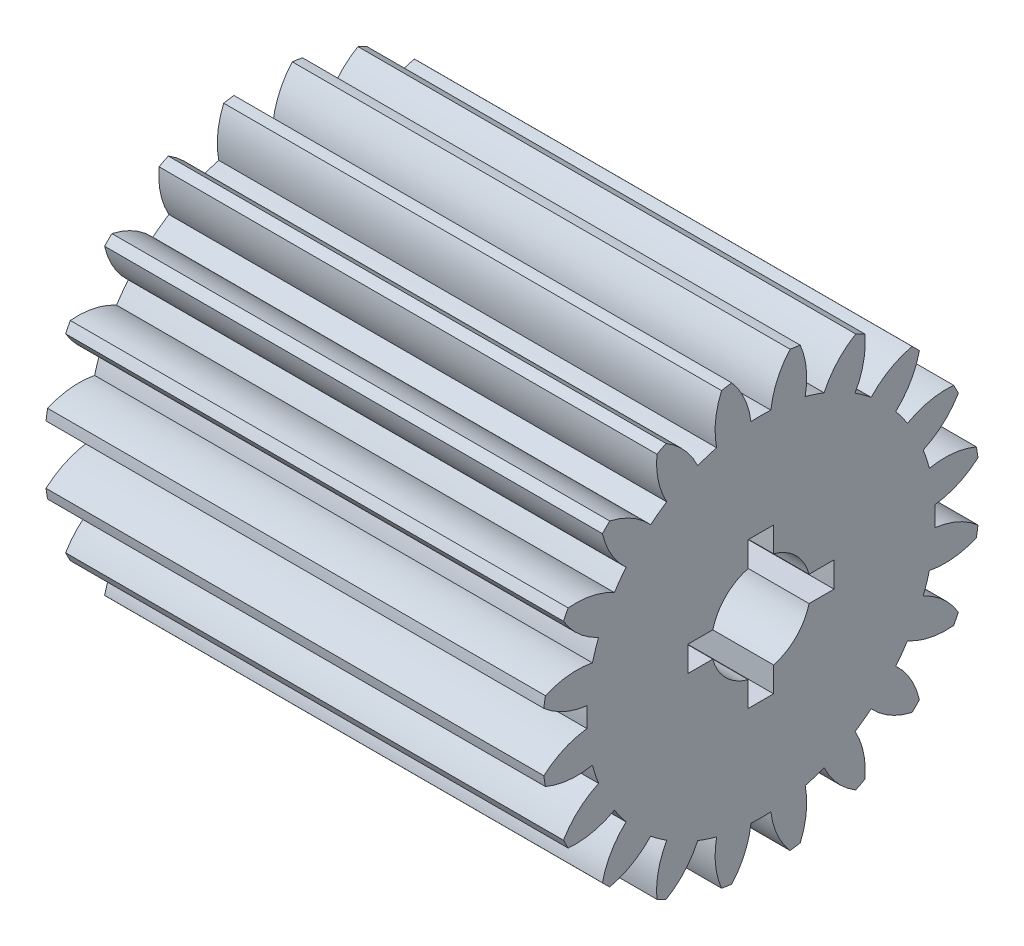
SolidWorks part; units mm, degrees
material "AISI 1020"
ref_plane "Plane1" through (0, 0, 0) normal (0, 0, 1) x (1, 0, 0)
ref_plane "Plane2" through (0, 0, 0) normal (0, 1, 0) x (1, 0, 0)
ref_plane "Plane3" through (0, 0, 0) normal (1, 0, 0) x (0, 0, -1)
other "Configuration Table"
sketch "HoldingSke" plane through (0, 0, 0) normal (0, 1, 0) x (1, 0, 0)
  line L0 (0, 0) -> (2.3492, -0.8551)
  line L1 (-15, 0) -> (100, 0) construction
  line L2 (0, 0) -> (-2.1039, 2.3779)
  line L3 (0, 0) -> (-11.863, 4.5341)
  line L4 (0, 0) -> (8.1152, 2.9537)
  line L5 (0, 0) -> (-46.8476, -17.4728)
  line L6 (0, 0) -> (-8.2896, -5.593)
  line L7 (-2.1039, 2.3779) -> (8.6586, 51.2059)
  line L8 (-76.2, 54.61) -> (-75.9, 54.61)
  line L9 (-71.009, 38.7566) -> (-53.1078, 45.2721)
  line L10 (-76.2, 71.12) -> (104.1128, 71.12)
  line L11 (0, 0) -> (-10, 0)
  line L12 (-76.2, 101.6) -> (-76.185, 101.6)
  line L13 (24.9733, 27.94) -> (52.9518, 28.4284)
  line L14 (24.9733, 27.94) -> (24.9743, 27.94)
  line L15 (24.9733, 27.94) -> (100.4006, 29.5858)
  line L16 (-63.627, -0.4) -> (-12.827, -0.4)
  circle A0 centre (0, 0) radius 1
  circle A1 centre (0, 0) radius 3.499
  circle A2 centre (0, 0) radius 37.5
  circle A3 centre (0, 0) radius 1
  dimension "Num_teeth" = 20
  dimension "Pitch_radius" = 180.3128
  dimension "Width" = 10
  dimension "Thickness" = 10
sketch "BasProSke" plane through (0, 0, 0) normal (0, 1, 0) x (1, 0, 0)
  line L0 (-10, 0) -> (60, 0) construction
  line L1 (0, 0) -> (0, 4.4)
  line L2 (0, 0) -> (10, 0)
  line L3 (10, 0) -> (10, 4.4)
  line L4 (10, 4.4) -> (0, 4.4)
  dimension "Thickness" = 10
  dimension "Diameter" = 8.8
revolve "Base-Revolve" add sketch "BasProSke" angle 360 about L0
sketch "TooCutSke" plane through (0, 0, 0) normal (1, 0, 0) x (0, 0, -1)
  line L1 (0, 0) -> (0, 107) construction
  line L2 (0, 0) -> (-0.3401, 3.9855) construction
  line L3 (0, 0) -> (-1.2482, 7.8811) construction
  line L4 (-0.3401, 3.9855) -> (-0.6241, 3.9405) construction
  arc A0 (0.1996, 3.4933) -> (-0.1996, 3.4933) centre (0, 0) ccw
  arc A1 (0.606, 4.3837) -> (-0.606, 4.3837) centre (0, 0) ccw
  circle A2 centre (0, 0) radius 4 construction
  circle A3 centre (0, 0) radius 3.7588 construction
  arc A4 (-0.1996, 3.4933) -> (-0.606, 4.3837) centre (-1.7886, 3.306) ccw
  arc A5 (0.606, 4.3837) -> (0.1996, 3.4933) centre (1.7886, 3.306) ccw
extrude "ToothCut" cut sketch "TooCutSke" along normal through all
fillet "Breaks" [suppressed] radius 0.008 tangent propagation no
fillet "RootFillets" [suppressed] radius 0.101
pattern_circular "TeethCuts" count 20 every 18 about axis through (-10, 0, 0) along (1, 0, 0) of "ToothCut", "RootFillets", "Breaks"
sketch "HubNeaOneSke" plane through (0, 0, 0) normal (-1, 0, 0) x (0, 0, 1)
  circle A0 centre (0, 0) radius 3.499
  dimension "Diameter" = 6.998
extrude "HubNearOne" [suppressed] add sketch "HubNeaOneSke" along normal blind 40.0001
sketch "HubNeaBotSke" plane through (0, 0, 0) normal (-1, 0, 0) x (0, 0, 1)
  circle A0 centre (0, 0) radius 3.499
  dimension "Diameter" = 6.998
extrude "HubNearBoth" [suppressed] add sketch "HubNeaBotSke" along normal blind 20
ref_plane "FarPln" through (10, 0, 0) normal (1, 0, 0) x (0, 0, -1)
sketch "HubFarSke" plane through (10, 0, 0) normal (1, 0, 0) x (0, 0, -1)
  circle A0 centre (0, 0) radius 3.499
  dimension "Diameter" = 6.998
extrude "HubFar" [suppressed] add sketch "HubFarSke" along normal blind 20
sketch "BorSke" plane through (0, 0, 0) normal (1, 0, 0) x (0, 0, -1)
  circle A0 centre (0, 0) radius 1
  dimension "Diameter" = 2
extrude "Bore" cut sketch "BorSke" along normal mid plane 100.0001
sketch "KeySke" plane through (0, 0, 0) normal (1, 0, 0) x (0, 0, -1)
  line L0 (-0.4, 0) -> (-0.4, 1.3)
  line L1 (-0.4, 1.3) -> (0.4, 1.3)
  line L2 (0.4, 1.3) -> (0.4, 0)
  line L3 (0, 0) -> (0, 34) construction
  line L4 (-0.4, 0) -> (0.4, 0)
  dimension "Width" = 0.8
extrude "Keyway" [suppressed] cut sketch "KeySke" along normal mid plane 100.0001
pattern_circular "Keyway2" [suppressed] count 2 every 90 about axis through (-10, 0, 0) along (1, 0, 0) reverse direction yes
sketch "Sketch1" plane through (10, 0, 0) normal (1, 0, 0) x (0, 0, -1)
  line L0 (-0.255, 0.9587) -> (0.255, 0.9587)
  line L1 (-0.255, 0.9587) -> (-0.255, 1.4687)
  line L2 (0.255, 0.9587) -> (0.255, 1.4687)
  line L3 (-0.255, 1.4687) -> (0.255, 1.4687)
  line L4 (0.9587, 0.255) -> (0.9587, -0.255)
  line L5 (0.9587, 0.255) -> (1.4687, 0.255)
  line L6 (0.9587, -0.255) -> (1.4687, -0.255)
  line L7 (1.4687, 0.255) -> (1.4687, -0.255)
  line L8 (0.255, -0.9587) -> (-0.255, -0.9587)
  line L9 (0.255, -0.9587) -> (0.255, -1.4687)
  line L10 (-0.255, -0.9587) -> (-0.255, -1.4687)
  line L11 (0.255, -1.4687) -> (-0.255, -1.4687)
  line L12 (-0.9587, -0.255) -> (-0.9587, 0.255)
  line L13 (-0.9587, -0.255) -> (-1.4687, -0.255)
  line L14 (-0.9587, 0.255) -> (-1.4687, 0.255)
  line L15 (-1.4687, -0.255) -> (-1.4687, 0.255)
  circle A0 centre (0, 0) radius 0.992
  dimension "D2" = 1.984
  dimension "D1" = 0.51
  dimension "D3" = 0.51
  dimension "D4" = 0.51
  dimension "D5" = 0.51
  dimension "D6" = 0.51
  dimension "D7" = 0.51
  dimension "D8" = 0.51
  dimension "D9" = 0.51
extrude "Cut-Extrude1" cut sketch "Sketch1" against normal blind 100 contours L3 L2 L0 L1 | L5 L7 L6 L4 | L9 L11 L10 L8 | L13 L15 L14 L12
equation "' \"Module@HoldingSke\" = 6.35"
equation "' \"Num_teeth@HoldingSke\" = 12"
equation "' \"Ap@HoldingSke\" =  20"
equation "' \"Ap@HoldingSke\" = 20"
equation "' \"Width@HoldingSke\" = 0.5 * 25.4"
equation "' \"Hub_dia@HoldingSke\"= 1 * 25.4"
equation "' \"Hub_dia@HoldingSke\" = 1 * 25.4"
equation "' \"Overall_len@HoldingSke\" = 1.0 * 25.4"
equation "' \"Bore@HoldingSke\" = 0.75 * 25.4"
equation "' \"T_dim@HoldingSke\" = 0.1 * 25.4"
equation "' \"Width@KeySke\" = 0.25 * 25.4"
equation "' \"Show_teeth@HoldingSke\" = 13"
equation "' \"Backlash@HoldingSke\" = 0.009 * 25.4"
equation "' \"Addendum_fac@HoldingSke\" = 1.0"
equation "' \"Dedendum_fac@HoldingSke\" = 1.25"
equation "' \"Dedendum_add@HoldingSke\" = 0.00005 * 25.4"
equation "' \"Clearance_fac@HoldingSke\" = 0.25"
equation "\"Pitch@HoldingSke\" = 1 / \"Module@HoldingSke\""
equation "\"Overcut_dia@TooCutSke\" = (\"Num_teeth@HoldingSke\" + 2 * \"Addendum_fac@HoldingSke\") / \"Pitch@HoldingSke\" + 0.002 * 25.4"
equation "\"Pitch_dia@TooCutSke\" = \"Num_teeth@HoldingSke\" / \"Pitch@HoldingSke\""
equation "\"Base_dia@TooCutSke\" = \"Num_teeth@HoldingSke\" / \"Pitch@HoldingSke\" * cos((\"Ap@HoldingSke\"  * 3.14159265 / 180))"
equation "\"Root_dia@TooCutSke\" = (\"Num_teeth@HoldingSke\" + 2) / \"Pitch@HoldingSke\" - 2 * (\"Addendum_fac@HoldingSke\" + \"Dedendum_fac@HoldingSke\") / \"Pitch@HoldingSke\" - \"Dedendum_add@HoldingSke\" * 2"
equation "\"Half_ang@TooCutSke\" = 180 / \"Num_teeth@HoldingSke\""
equation "\"Half_CT@TooCutSke\" = \"Num_teeth@HoldingSke\" / \"Pitch@HoldingSke\" * sin((3.14159265 / 2 / \"Num_teeth@HoldingSke\")) / 2 - 7 * \"Backlash@HoldingSke\" / 4"
equation "\"Flank_rad@TooCutSke\" = \"Num_teeth@HoldingSke\" / \"Pitch@HoldingSke\" / 5"
equation "\"Radius@RootFillets\" = \"Clearance_fac@HoldingSke\" / \"Pitch@HoldingSke\" + \"Dedendum_add@HoldingSke\""
equation "\"Break_rad@Breaks\" = 0.02 / \"Pitch@HoldingSke\""
equation "\"Thickness@HoldingSke\" = \"Width@HoldingSke\""
equation "\"OAL@HoldingSke\" = \"Thickness@HoldingSke\""
equation "\"MHD@HoldingSke\" = (\"Num_teeth@HoldingSke\" + 2) / \"Pitch@HoldingSke\" - 2 * (\"Addendum_fac@HoldingSke\" + \"Dedendum_fac@HoldingSke\")  / \"Pitch@HoldingSke\" - \"Dedendum_add@HoldingSke\" * 2"
equation "\"MBD@HoldingSke\" = (\"Num_teeth@HoldingSke\" + 2) / \"Pitch@HoldingSke\" - 2 * (\"Addendum_fac@HoldingSke\" + \"Dedendum_fac@HoldingSke\")  / \"Pitch@HoldingSke\" - \"Dedendum_add@HoldingSke\" * 2 - 0.002 * 25.4"
equation "\"MHD@HoldingSke\" = ((sgn( \"MHD@HoldingSke\" - \"Hub_dia@HoldingSke\" )-1)*( \"MHD@HoldingSke\" - \"Hub_dia@HoldingSke\" ))/-2+ \"Hub_dia@HoldingSke\""
equation "\"MBD@HoldingSke\" = ((sgn( \"MBD@HoldingSke\" - \"Bore@HoldingSke\" )-1)*( \"MBD@HoldingSke\" - \"Bore@HoldingSke\" ))/-2+ \"Bore@HoldingSke\""
equation "\"OAL@HoldingSke\" = ((sgn( \"OAL@HoldingSke\" - \"Overall_len@HoldingSke\" )+1)*( \"OAL@HoldingSke\" - \"Overall_len@HoldingSke\" ))/2 + \"Overall_len@HoldingSke\" + 0.000002 * 25.4"
equation "\"Num_teeth@TeethCuts\" = int( \"Show_teeth@HoldingSke\" ) + 1"
equation "\"Num_teeth@TeethCuts\" = ((sgn( \"Num_teeth@TeethCuts\" - \"Num_teeth@HoldingSke\" )-1)*( \"Num_teeth@TeethCuts\" - \"Num_teeth@HoldingSke\" ))/-2+ \"Num_teeth@HoldingSke\""
equation "\"Num_teeth@TeethCuts\" = ((sgn( \"Num_teeth@TeethCuts\" - 2.0)+1)*( \"Num_teeth@TeethCuts\" - 2.0))/2 +2.0"
equation "\"Angle@TeethCuts\" = 360.0 / \"Num_teeth@HoldingSke\""
equation "\"Diameter@BasProSke\" = (\"Num_teeth@HoldingSke\" + 2 * \"Addendum_fac@HoldingSke\") / \"Pitch@HoldingSke\""
equation "\"Thickness@BasProSke\"  = \"Thickness@HoldingSke\""
equation "' \"Fillet_rad@BasProSke\" =  \"Thickness@HoldingSke\" * 0.05"
equation "' \"Fillet_rad@BasProSke\" = \"Thickness@HoldingSke\" * 0.05"
equation "\"MHD@HoldingSke\" = ((sgn( \"MHD@HoldingSke\" - \"Root_dia@TooCutSke\" )-1)*( \"MHD@HoldingSke\" - \"Root_dia@TooCutSke\" ))/-2+ \"Root_dia@TooCutSke\""
equation "\"Diameter@HubNeaOneSke\" = \"MHD@HoldingSke\""
equation "\"Length@HubNearOne\" = \"OAL@HoldingSke\" - \"Thickness@BasProSke\""
equation "\"Diameter@HubNeaBotSke\" = \"MHD@HoldingSke\""
equation "\"Length@HubNearBoth\" = ( \"OAL@HoldingSke\" - \"Thickness@BasProSke\" ) / 2.0"
equation "\"Thickness@FarPln\" = \"Thickness@BasProSke\""
equation "\"Diameter@HubFarSke\" = \"MHD@HoldingSke\""
equation "\"Length@HubFar\" = ( \"OAL@HoldingSke\" - \"Thickness@BasProSke\" ) / 2.0"
equation "\"Diameter@BorSke\" = \"MBD@HoldingSke\""
equation "\"D1@Bore\" = \"OAL@HoldingSke\" * 2.0"
equation "\"D1@Keyway\" = \"OAL@HoldingSke\" * 2.0"
equation "\"Offset@KeySke\" = \"T_dim@HoldingSke\" + \"MBD@HoldingSke\" / 2.0"
